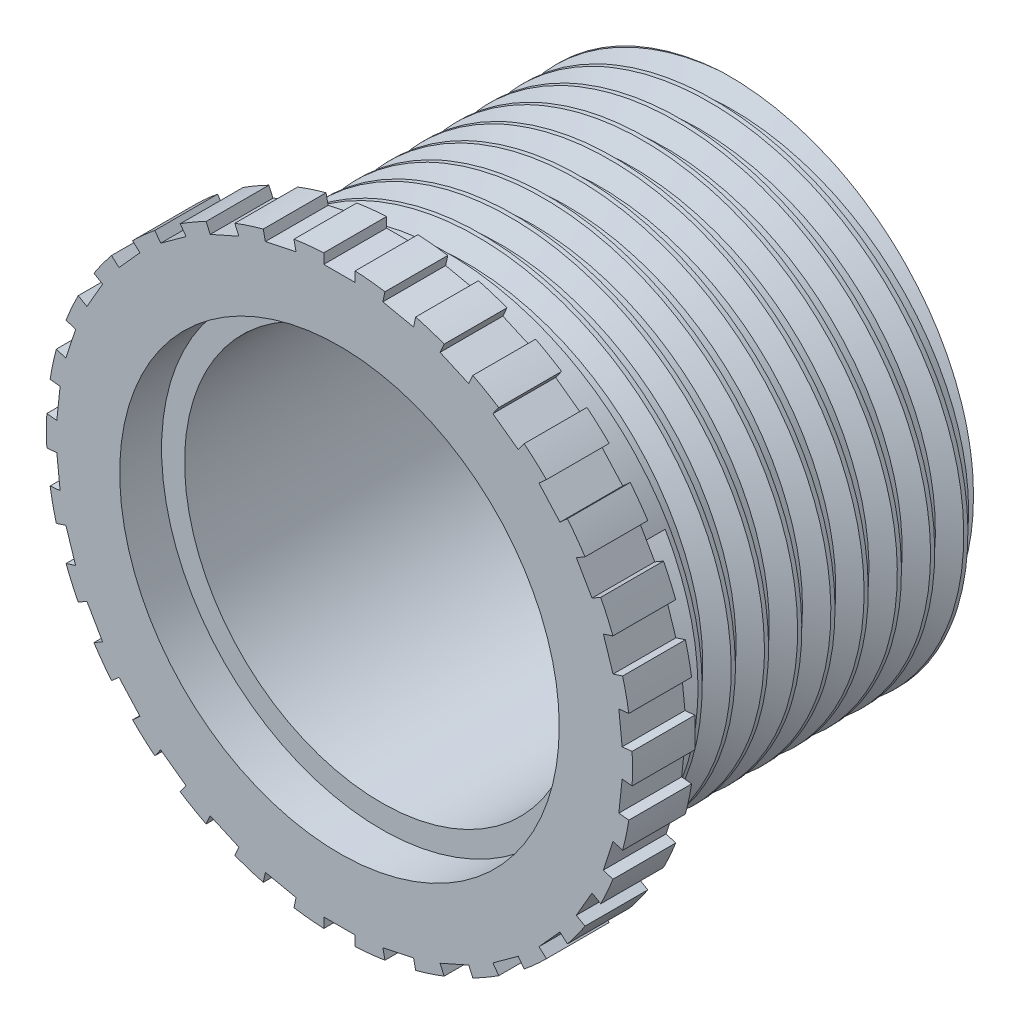
SolidWorks part; units mm, degrees
ref_plane "Plan de face" through (0, 0, 0) normal (0, 0, 1) x (1, 0, 0)
ref_plane "Plan de dessus" through (0, 0, 0) normal (0, 1, 0) x (1, 0, 0)
ref_plane "Plan de droite" through (0, 0, 0) normal (1, 0, 0) x (0, 0, -1)
sketch "Esquisse1" plane through (0, 0, 0) normal (0, 0, 1) x (1, 0, 0)
  circle A0 centre (0, 0) radius 6
extrude "Boss.-Extru.1" add sketch "Esquisse1" along normal blind 8
sketch "Esquisse2" plane through (0, 0, 8) normal (0, 0, 1) x (1, 0, 0)
  circle A2 centre (0, 0) radius 5
  circle A3 centre (0, 0) radius 5
  dimension "D1" = 1
extrude "Enlèv. mat.-Extru.1" cut sketch "Esquisse2" against normal blind 8
sketch "Esquisse3" plane through (0, 0, 8) normal (0, 0, 1) x (1, 0, 0)
  circle A0 centre (0, 0) radius 7
  circle A1 centre (0, 0) radius 5
extrude "Boss.-Extru.2" add sketch "Esquisse3" along normal blind 1.5
sketch "Esquisse4" plane through (0, 0, 9.5) normal (0, 0, 1) x (1, 0, 0)
  line L0 (1.1406, 7.1695) -> (1.0366, 6.6805)
  line L1 (-0.375, 7.25) -> (0.375, 7.25)
  line L2 (-0.375, 7.25) -> (-0.375, 6.75)
  line L3 (-0.375, 6.75) -> (0.375, 6.75)
  line L4 (0.375, 7.25) -> (0.375, 6.75)
  line L5 (-0.375, 7.25) -> (0.375, 6.75) construction
  line L6 (-0.375, 6.75) -> (0.375, 7.25) construction
  line L7 (1.1406, 7.1695) -> (1.8742, 7.0136)
  line L8 (1.8742, 7.0136) -> (1.7702, 6.5245)
  line L9 (1.0366, 6.6805) -> (1.7702, 6.5245)
  line L10 (2.6063, 6.7757) -> (2.4029, 6.319)
  line L11 (2.6063, 6.7757) -> (3.2914, 6.4707)
  line L12 (3.2914, 6.4707) -> (3.0881, 6.0139)
  line L13 (2.4029, 6.319) -> (3.0881, 6.0139)
  line L14 (3.9581, 6.0858) -> (3.6642, 5.6813)
  line L15 (3.9581, 6.0858) -> (4.5648, 5.645)
  line L16 (4.5648, 5.645) -> (4.2709, 5.2404)
  line L17 (3.6642, 5.6813) -> (4.2709, 5.2404)
  line L18 (5.1369, 5.1299) -> (4.7653, 4.7953)
  line L19 (5.1369, 5.1299) -> (5.6387, 4.5725)
  line L20 (5.6387, 4.5725) -> (5.2672, 4.238)
  line L21 (4.7653, 4.7953) -> (5.2672, 4.238)
  line L22 (6.0912, 3.9498) -> (5.6582, 3.6998)
  line L23 (6.0912, 3.9498) -> (6.4662, 3.3002)
  line L24 (6.4662, 3.3002) -> (6.0332, 3.0502)
  line L25 (5.6582, 3.6998) -> (6.0332, 3.0502)
  line L26 (6.7793, 2.597) -> (6.3038, 2.4425)
  line L27 (6.7793, 2.597) -> (7.011, 1.8837)
  line L28 (7.011, 1.8837) -> (6.5355, 1.7292)
  line L29 (6.3038, 2.4425) -> (6.5355, 1.7292)
  line L30 (7.1711, 1.1308) -> (6.6738, 1.0785)
  line L31 (7.1711, 1.1308) -> (7.2495, 0.3849)
  line L32 (7.2495, 0.3849) -> (6.7522, 0.3326)
  line L33 (6.6738, 1.0785) -> (6.7522, 0.3326)
  line L34 (7.2495, -0.3849) -> (6.7522, -0.3326)
  line L35 (7.2495, -0.3849) -> (7.1711, -1.1308)
  line L36 (7.1711, -1.1308) -> (6.6738, -1.0785)
  line L37 (6.7522, -0.3326) -> (6.6738, -1.0785)
  line L38 (7.011, -1.8837) -> (6.5355, -1.7292)
  line L39 (7.011, -1.8837) -> (6.7793, -2.597)
  line L40 (6.7793, -2.597) -> (6.3038, -2.4425)
  line L41 (6.5355, -1.7292) -> (6.3038, -2.4425)
  line L42 (6.4662, -3.3002) -> (6.0332, -3.0502)
  line L43 (6.4662, -3.3002) -> (6.0912, -3.9498)
  line L44 (6.0912, -3.9498) -> (5.6582, -3.6998)
  line L45 (6.0332, -3.0502) -> (5.6582, -3.6998)
  line L46 (5.6387, -4.5725) -> (5.2672, -4.238)
  line L47 (5.6387, -4.5725) -> (5.1369, -5.1299)
  line L48 (5.1369, -5.1299) -> (4.7653, -4.7953)
  line L49 (5.2672, -4.238) -> (4.7653, -4.7953)
  line L50 (4.5648, -5.645) -> (4.2709, -5.2404)
  line L51 (4.5648, -5.645) -> (3.9581, -6.0858)
  line L52 (3.9581, -6.0858) -> (3.6642, -5.6813)
  line L53 (4.2709, -5.2404) -> (3.6642, -5.6813)
  line L54 (3.2914, -6.4707) -> (3.0881, -6.0139)
  line L55 (3.2914, -6.4707) -> (2.6063, -6.7757)
  line L56 (2.6063, -6.7757) -> (2.4029, -6.319)
  line L57 (3.0881, -6.0139) -> (2.4029, -6.319)
  line L58 (1.8742, -7.0136) -> (1.7702, -6.5245)
  line L59 (1.8742, -7.0136) -> (1.1406, -7.1695)
  line L60 (1.1406, -7.1695) -> (1.0366, -6.6805)
  line L61 (1.7702, -6.5245) -> (1.0366, -6.6805)
  line L62 (0.375, -7.25) -> (0.375, -6.75)
  line L63 (0.375, -7.25) -> (-0.375, -7.25)
  line L64 (-0.375, -7.25) -> (-0.375, -6.75)
  line L65 (0.375, -6.75) -> (-0.375, -6.75)
  line L66 (-1.1406, -7.1695) -> (-1.0366, -6.6805)
  line L67 (-1.1406, -7.1695) -> (-1.8742, -7.0136)
  line L68 (-1.8742, -7.0136) -> (-1.7702, -6.5245)
  line L69 (-1.0366, -6.6805) -> (-1.7702, -6.5245)
  line L70 (-2.6063, -6.7757) -> (-2.4029, -6.319)
  line L71 (-2.6063, -6.7757) -> (-3.2914, -6.4707)
  line L72 (-3.2914, -6.4707) -> (-3.0881, -6.0139)
  line L73 (-2.4029, -6.319) -> (-3.0881, -6.0139)
  line L74 (-3.9581, -6.0858) -> (-3.6642, -5.6813)
  line L75 (-3.9581, -6.0858) -> (-4.5648, -5.645)
  line L76 (-4.5648, -5.645) -> (-4.2709, -5.2404)
  line L77 (-3.6642, -5.6813) -> (-4.2709, -5.2404)
  line L78 (-5.1369, -5.1299) -> (-4.7653, -4.7953)
  line L79 (-5.1369, -5.1299) -> (-5.6387, -4.5725)
  line L80 (-5.6387, -4.5725) -> (-5.2672, -4.238)
  line L81 (-4.7653, -4.7953) -> (-5.2672, -4.238)
  line L82 (-6.0912, -3.9498) -> (-5.6582, -3.6998)
  line L83 (-6.0912, -3.9498) -> (-6.4662, -3.3002)
  line L84 (-6.4662, -3.3002) -> (-6.0332, -3.0502)
  line L85 (-5.6582, -3.6998) -> (-6.0332, -3.0502)
  line L86 (-6.7793, -2.597) -> (-6.3038, -2.4425)
  line L87 (-6.7793, -2.597) -> (-7.011, -1.8837)
  line L88 (-7.011, -1.8837) -> (-6.5355, -1.7292)
  line L89 (-6.3038, -2.4425) -> (-6.5355, -1.7292)
  line L90 (-7.1711, -1.1308) -> (-6.6738, -1.0785)
  line L91 (-7.1711, -1.1308) -> (-7.2495, -0.3849)
  line L92 (-7.2495, -0.3849) -> (-6.7522, -0.3326)
  line L93 (-6.6738, -1.0785) -> (-6.7522, -0.3326)
  line L94 (-7.2495, 0.3849) -> (-6.7522, 0.3326)
  line L95 (-7.2495, 0.3849) -> (-7.1711, 1.1308)
  line L96 (-7.1711, 1.1308) -> (-6.6738, 1.0785)
  line L97 (-6.7522, 0.3326) -> (-6.6738, 1.0785)
  line L98 (-7.011, 1.8837) -> (-6.5355, 1.7292)
  line L99 (-7.011, 1.8837) -> (-6.7793, 2.597)
  line L100 (-6.7793, 2.597) -> (-6.3038, 2.4425)
  line L101 (-6.5355, 1.7292) -> (-6.3038, 2.4425)
  line L102 (-6.4662, 3.3002) -> (-6.0332, 3.0502)
  line L103 (-6.4662, 3.3002) -> (-6.0912, 3.9498)
  line L104 (-6.0912, 3.9498) -> (-5.6582, 3.6998)
  line L105 (-6.0332, 3.0502) -> (-5.6582, 3.6998)
  line L106 (-5.6387, 4.5725) -> (-5.2672, 4.238)
  line L107 (-5.6387, 4.5725) -> (-5.1369, 5.1299)
  line L108 (-5.1369, 5.1299) -> (-4.7653, 4.7953)
  line L109 (-5.2672, 4.238) -> (-4.7653, 4.7953)
  line L110 (-4.5648, 5.645) -> (-4.2709, 5.2404)
  line L111 (-4.5648, 5.645) -> (-3.9581, 6.0858)
  line L112 (-3.9581, 6.0858) -> (-3.6642, 5.6813)
  line L113 (-4.2709, 5.2404) -> (-3.6642, 5.6813)
  line L114 (-3.2914, 6.4707) -> (-3.0881, 6.0139)
  line L115 (-3.2914, 6.4707) -> (-2.6063, 6.7757)
  line L116 (-2.6063, 6.7757) -> (-2.4029, 6.319)
  line L117 (-3.0881, 6.0139) -> (-2.4029, 6.319)
  line L118 (-1.8742, 7.0136) -> (-1.7702, 6.5245)
  line L119 (-1.8742, 7.0136) -> (-1.1406, 7.1695)
  line L120 (-1.1406, 7.1695) -> (-1.0366, 6.6805)
  line L121 (-1.7702, 6.5245) -> (-1.0366, 6.6805)
  circle A0 centre (0, 0) radius 7 construction
  point P0 (0, 7)
  dimension "D1" = 0.5
  dimension "D2" = 0.75
  dimension "D3" = 30
extrude "Enlèv. mat.-Extru.2" cut sketch "Esquisse4" against normal blind 1.5
sketch "Esquisse5" plane through (0, 0, 9.5) normal (0, 0, 1) x (1, 0, 0)
  circle A0 centre (0, 0) radius 5
  circle A1 centre (0, 0) radius 4.7
extrude "Boss.-Extru.3" add sketch "Esquisse5" against normal up to surface (9.5 mm away) from offset 0.5 up to face at (5, 0, 0) offset against normal yes
thread "Filetage1" pitch 0.7937 method cut profile "Profil de filetage1" start angle 0, offset 1, length 8, pitch 0.7937, diameter 12
ref_plane "Plan1" through (6, 0, -1) normal (0, -1, 0) x (1, 0, 0)
sketch "Profil de filetage1" plane through (6, 0, -1) normal (0, -1, 0) x (1, 0, 0)
  line L0 (0, 0) -> (0, 0.7937) construction
  line L11 (0, 0) -> (0, 0.6945)
  line L12 (0, 0.6945) -> (-0.4296, 0.4465)
  line L13 (-0.4296, 0.4465) -> (-0.4296, 0.248)
  line L15 (-0.4296, 0.248) -> (0, 0)
  line L17 (-0.4296, 0.3473) -> (0, 0.3473) construction
  point P2 (0, 0)
  dimension "Pitch" = 0.7937
  dimension "Profile_Angle" = 60
  dimension "Profile_Land" = 0.1984
  dimension "Profile_Height" = 0.4296
sketch "Esquisse6" plane through (0, 0, 9.5) normal (0, 0, 1) x (1, 0, 0)
  circle A0 centre (0, 0) radius 5.25
extrude "Enlèv. mat.-Extru.3" cut sketch "Esquisse6" against normal blind 1
